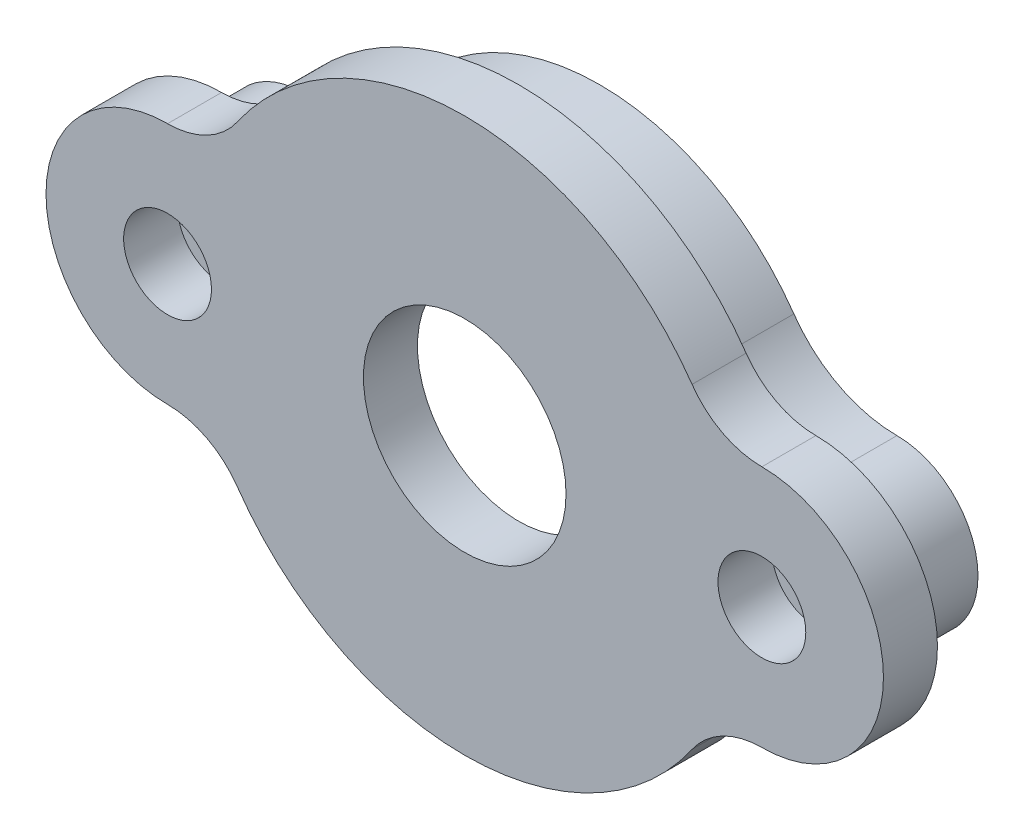
SolidWorks part; units mm, degrees
ref_plane "Ön Düzlem" through (0, 0, 0) normal (0, 0, 1) x (1, 0, 0)
ref_plane "Üst Düzlem" through (0, 0, 0) normal (0, 1, 0) x (1, 0, 0)
ref_plane "Sağ Düzlem" through (0, 0, 0) normal (1, 0, 0) x (0, 0, -1)
sketch "Sketch1" plane through (0, 0, 0) normal (0, 0, 1) x (1, 0, 0)
  circle A0 centre (0, 0) radius 16
  circle A1 centre (0, 0) radius 7.5
  arc A2 (-22, 6) -> (-22, -6) centre (-22, 0) ccw
  arc A3 (22, -6) -> (22, 6) centre (22, 0) ccw
  arc A4 (-22, 6) -> (-14.3692, 9.9888) centre (-22, 15.2935) ccw
  arc A5 (22, 6) -> (14.3692, 9.9888) centre (22, 15.2935) cw
  arc A6 (-22, -6) -> (-14.3692, -9.9888) centre (-22, -15.2935) cw
  arc A7 (22, -6) -> (14.3692, -9.9888) centre (22, -15.2935) ccw
  arc A8 (-14.3692, 9.9888) -> (14.3692, 9.9888) centre (0, 0) cw
  arc A9 (-14.3692, -9.9888) -> (14.3692, -9.9888) centre (0, 0) ccw
  arc A10 (-22, 9) -> (-22, -9) centre (-22, 0) ccw
  arc A11 (-22, -9) -> (-16.8325, -11.7012) centre (-22, -15.2935) cw
  arc A12 (-16.8325, -11.7012) -> (16.8325, -11.7012) centre (0, 0) ccw
  arc A13 (22, -9) -> (16.8325, -11.7012) centre (22, -15.2935) ccw
  arc A14 (22, -9) -> (22, 9) centre (22, 0) ccw
  arc A15 (22, 9) -> (16.8325, 11.7012) centre (22, 15.2935) cw
  arc A16 (-16.8325, 11.7012) -> (16.8325, 11.7012) centre (0, 0) cw
  arc A17 (-22, 9) -> (-16.8325, 11.7012) centre (-22, 15.2935) ccw
  point P5 (-22, -1.0167)
  point P7 (22, 0)
  point P22 (16.5084, 19.8232)
  point P23 (16.5084, -17.5965)
  point P24 (15.4817, 8.1588)
  point P25 (-34.2594, -1.1807)
  point P26 (41.2733, 0)
  point P27 (14.629, 9.6043)
  dimension "D1" = 32
  dimension "D2" = 15
  dimension "D3" = 1.5
  dimension "D4" = 1.5
  dimension "D7" = 6
  dimension "D8" = 6
  dimension "D5" = 22
  dimension "D6" = 22
  dimension "D9" = 3
extrude "Boss-Extrude1" add sketch "Sketch1" along normal blind 10 contours A17 A10 A11 A12 A13 A14 A15 A16 A9 A6 A2 A4 A8 A5 A3 A7 | A6 A9 A7 A3 A5 A8 A4 A2 A0 | A0 A1 | A1 region at (-15.5475, 0, 0) region at (0, 0, 0) region at (-17.3888, 6.4721, 0) region at (-18.7402, 9.0573, 0)
extrude "Cut-Extrude1" cut sketch "Sketch1<3>" along normal blind 6 contours A0 A1 region at (-15.5475, 0, 0)
sketch "Sketch1<3>" plane through (0, 0, 0) normal (0, 0, 1) x (1, 0, 0) same geometry as "Sketch1"
extrude "Cut-Extrude2" cut sketch "Sketch1<4>" along normal blind 10 contours A1 region at (0, 0, 0)
sketch "Sketch1<4>" plane through (0, 0, 0) normal (0, 0, 1) x (1, 0, 0) same geometry as "Sketch1"
extrude "Cut-Extrude3" cut sketch "Sketch1<5>" along normal blind 6 contours A17 A10 A11 A12 A13 A14 A15 A16 A9 A6 A2 A4 A8 A5 A3 A7 region at (-18.7402, 9.0573, 0)
sketch "Sketch1<5>" plane through (0, 0, 0) normal (0, 0, 1) x (1, 0, 0) same geometry as "Sketch1"
sketch "Sketch3" plane through (0, 0, 10) normal (0, 0, 1) x (1, 0, 0)
  circle A0 centre (22, 0) radius 1.75
  circle A1 centre (-22, 0) radius 1.75
  dimension "D1" = 3.5
  dimension "D2" = 3.5
extrude "Cut-Extrude4" cut sketch "Sketch3" against normal blind 10
sketch "Sketch4" plane through (0, 0, 10) normal (0, 0, 1) x (1, 0, 0)
  circle A0 centre (22, 0) radius 3.25
  circle A1 centre (-22, 0) radius 3.25
  dimension "D1" = 6.5
  dimension "D2" = 6.5
extrude "Cut-Extrude5" cut sketch "Sketch4" against normal blind 4
